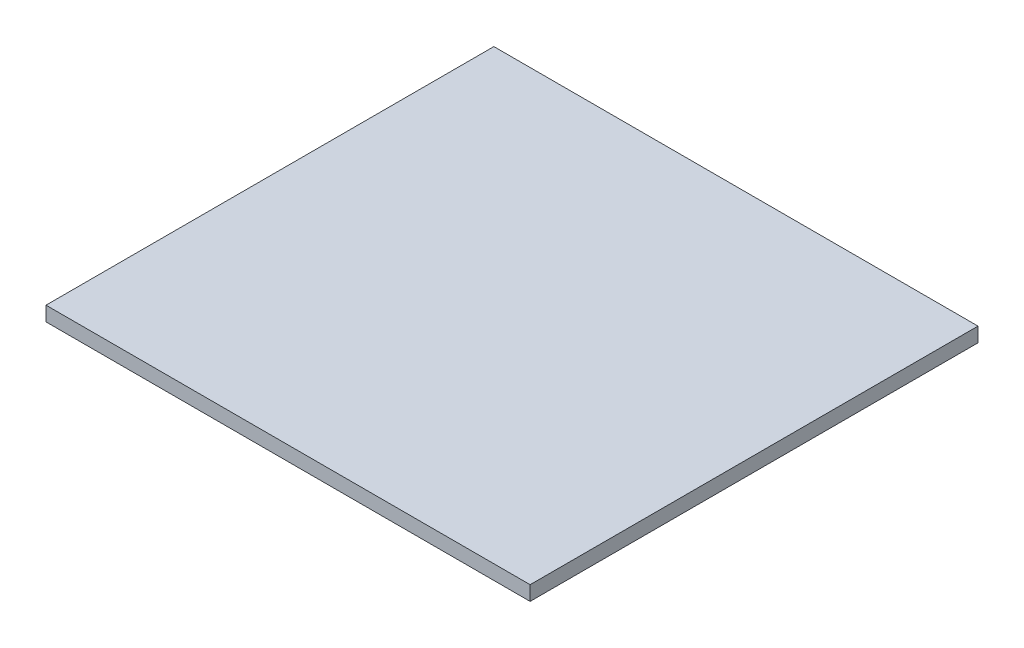
SolidWorks part; units mm, degrees
ref_plane "Front Plane" through (0, 0, 0) normal (0, 0, 1) x (1, 0, 0)
ref_plane "Top Plane" through (0, 0, 0) normal (0, 1, 0) x (1, 0, 0)
ref_plane "Right Plane" through (0, 0, 0) normal (1, 0, 0) x (0, 0, -1)
sketch "Sketch1" plane through (0, 0, 0) normal (0, 1, 0) x (1, 0, 0)
  line L1 (0, 0) -> (66.76, 0)
  line L2 (0, 0) -> (0, 61.76)
  line L3 (0, 61.76) -> (66.76, 61.76)
  line L4 (66.76, 0) -> (66.76, 61.76)
  dimension "D1" = 66.76
  dimension "D2" = 61.76
extrude "Boss-Extrude3" add sketch "Sketch1" along normal blind 2
